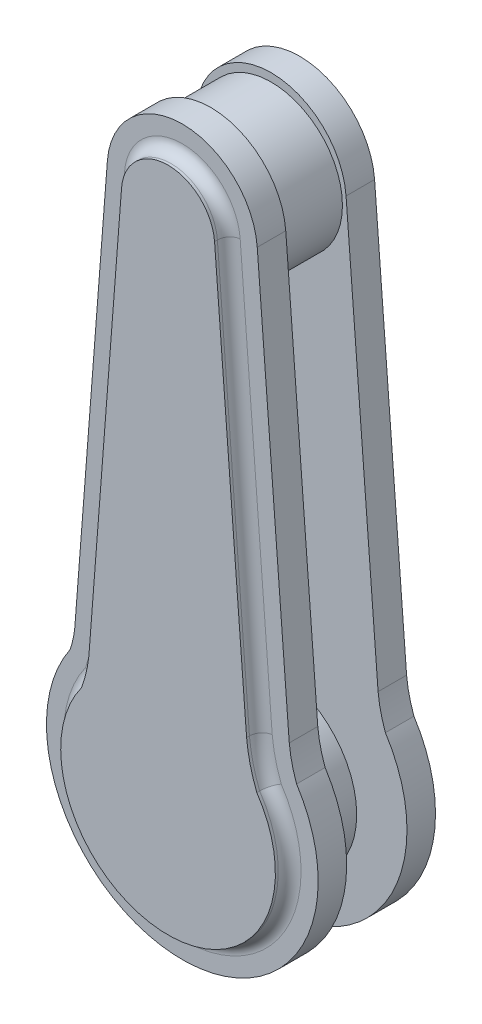
SolidWorks part; units mm, degrees
ref_plane "前视基准面" through (0, 0, 0) normal (0, 0, 1) x (1, 0, 0)
ref_plane "上视基准面" through (0, 0, 0) normal (0, 1, 0) x (1, 0, 0)
ref_plane "右视基准面" through (0, 0, 0) normal (1, 0, 0) x (0, 0, -1)
other "Configuration Table"
sketch "草图1" plane through (0, 0, 0) normal (0, 0, 1) x (1, 0, 0)
  circle A0 centre (0, -26.4271) radius 60
  circle A1 centre (0, 338.5729) radius 50
  circle A2 centre (0, -26.4271) radius 46.25
  circle A3 centre (0, 338.5729) radius 46.25
  dimension "D1" = 120
  dimension "D2" = 100
  dimension "D4" = 92.5
  dimension "D5" = 92.5
  dimension "D3" = 365
extrude "凸台-拉伸1" add sketch "草图1" along normal blind 21.15
sketch "草图2" plane through (0, 0, 21.15) normal (0, 0, 1) x (1, 0, 0)
  line L0 (52.5427, 345.6271) -> (75.0043, 55.7845)
  line L1 (-0.0104, 631.0617) -> (-0.0104, -200.849) construction
  line L2 (-52.5635, 345.6271) -> (-75.4877, 49.8143)
  arc A4 (-52.5635, 345.6271) -> (52.5427, 345.6271) centre (-0.0104, 341.5544) cw
  arc A12 (-78.6868, 35.6562) -> (80.1591, 33.403) centre (-0.0104, -18.1022) ccw
  arc A13 (75.0043, 55.7845) -> (80.1591, 33.403) centre (162.7197, 64.2024) ccw
  arc A14 (-75.4877, 49.8143) -> (-78.6868, 35.6562) centre (-145.836, 58.269) cw
extrude "凸台-拉伸2" add sketch "草图2" along normal blind 20
sketch "草图3" plane through (0, 0, 41.15) normal (0, 0, 1) x (1, 0, 0)
  line L4 (55.0775, 54.0658) -> (32.6025, 344.0818)
  line L5 (-32.6233, 344.0818) -> (-55.5782, 47.8737)
  line L6 (55.0775, 54.0658) -> (32.6025, 344.0818)
  line L7 (-32.6233, 344.0818) -> (-55.5782, 47.8737)
  arc A2 (32.6025, 344.0818) -> (-32.6233, 344.0818) centre (-0.0104, 341.5544) ccw
  arc A3 (32.6025, 344.0818) -> (-32.6233, 344.0818) centre (-0.0104, 341.5544) ccw
  arc A4 (55.0775, 54.0658) -> (62.2782, 24.1886) centre (162.7197, 64.2024) ccw
  arc A10 (55.0775, 54.0658) -> (62.2782, 24.1886) centre (162.7197, 64.2024) ccw
  arc A17 (-60.7704, 26.3568) -> (-55.5782, 47.8737) centre (-145.836, 58.269) ccw
  arc A19 (-60.7704, 26.3568) -> (-55.5782, 47.8737) centre (-145.836, 58.269) ccw
  arc A20 (-60.7704, 26.3568) -> (62.2782, 24.1886) centre (-0.0104, -18.1022) ccw
  arc A21 (-60.7704, 26.3568) -> (62.2782, 24.1886) centre (-0.0104, -18.1022) ccw
  dimension "D1" = 20
sketch "草图9" plane through (0, 0, 41.15) normal (0, 0, 1) x (1, 0, 0)
  line L4 (-32.6233, 344.0818) -> (-55.5782, 47.8737)
  line L5 (55.0775, 54.0658) -> (32.6025, 344.0818)
  line L6 (-32.6233, 344.0818) -> (-55.5782, 47.8737)
  line L7 (55.0775, 54.0658) -> (32.6025, 344.0818)
  arc A4 (32.6025, 344.0818) -> (-32.6233, 344.0818) centre (-0.0104, 341.5544) ccw
  arc A5 (55.0775, 54.0658) -> (62.2782, 24.1886) centre (162.7197, 64.2024) ccw
  arc A6 (32.6025, 344.0818) -> (-32.6233, 344.0818) centre (-0.0104, 341.5544) ccw
  arc A12 (55.0775, 54.0658) -> (62.2782, 24.1886) centre (162.7197, 64.2024) ccw
  arc A15 (-60.7704, 26.3568) -> (-55.5782, 47.8737) centre (-145.836, 58.269) ccw
  arc A17 (-60.7704, 26.3568) -> (-55.5782, 47.8737) centre (-145.836, 58.269) ccw
  arc A18 (-60.7704, 26.3568) -> (62.2782, 24.1886) centre (-0.0104, -18.1022) ccw
  arc A19 (-60.7704, 26.3568) -> (62.2782, 24.1886) centre (-0.0104, -18.1022) ccw
  dimension "D1" = 20
extrude "凸台-拉伸6" add sketch "草图9" along normal blind 10
fillet "圆角5" radius 8 6 edges at (43.84, 199.0738, 41.15) (-0.0104, 374.2651, 41.15) (-44.1007, 195.9777, 41.15) (57.6109, 38.87, 41.15) (-57.5166, 36.9565, 41.15) (-1.3369, -93.3791, 41.15)
ref_plane "基准面3" through (0, 0, 0) normal (0, 0, -1) x (-1, 0, 0)
sketch "草图10" plane through (0, 0, 41.15) normal (0, 0, 1) x (1, 0, 0)
mirror "镜向18" about plane through (0, 0, 0) normal (0, 0, -1) of "凸台-拉伸1", "凸台-拉伸2", "凸台-拉伸6", "圆角5"
extrude "凸台-拉伸3" add sketch "草图3" along normal blind 10
